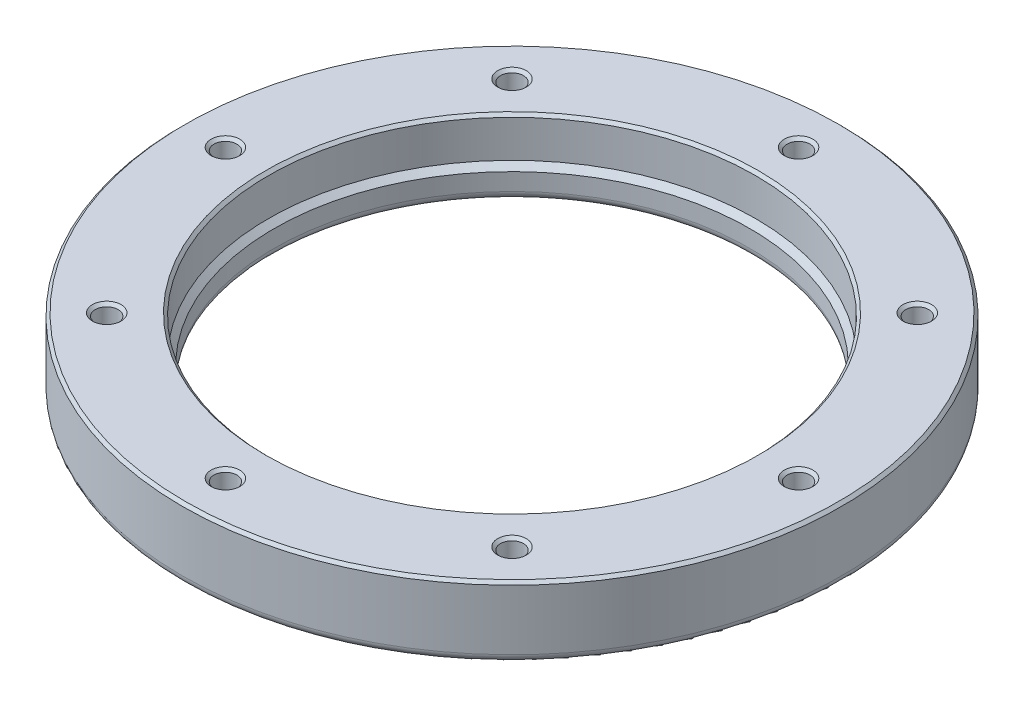
SolidWorks part; units mm, degrees
ref_plane "Front Plane" through (0, 0, 0) normal (0, 0, 1) x (1, 0, 0)
ref_plane "Top Plane" through (0, 0, 0) normal (0, 1, 0) x (1, 0, 0)
ref_plane "Right Plane" through (0, 0, 0) normal (1, 0, 0) x (0, 0, -1)
sketch "Sketch2" plane through (0, 0, 0) normal (0, 1, 0) x (1, 0, 0)
  circle A0 centre (0, 0) radius 115
  dimension "D1" = 230
extrude "Boss-Extrude1" add sketch "Sketch2" along normal blind 25
sketch "Sketch3" plane through (0, 25, 0) normal (0, 1, 0) x (1, 0, 0)
  circle A0 centre (0, 0) radius 85
  dimension "D1" = 170
extrude "Cut-Extrude1" cut sketch "Sketch3" against normal blind 16
sketch "Sketch4" plane through (0, 9, 0) normal (0, 1, 0) x (1, 0, 0)
  circle A0 centre (0, 0) radius 83
  dimension "D1" = 166
extrude "Cut-Extrude2" cut sketch "Sketch4" against normal through all
chamfer "Chamfer3" distance 2 angle 45 1 edges at (0, 9, 85)
chamfer "Chamfer5" distance 1 angle 45 2 edges at (0, 25, 85) (0, 25, 115)
fillet "Fillet1" radius 3 2 edges at (0, 0, 83) (0, 0, 115)
sketch "Sketch5" plane through (0, 25, 0) normal (0, 1, 0) x (1, 0, 0)
  line L0 (0, 0) -> (-169.6567, 0) construction
  circle A0 centre (-100, 0) radius 4
  circle A1 centre (-70.7107, 70.7107) radius 4
  circle A2 centre (0, 100) radius 4
  circle A3 centre (70.7107, 70.7107) radius 4
  circle A4 centre (100, 0) radius 4
  circle A5 centre (70.7107, -70.7107) radius 4
  circle A6 centre (0, -100) radius 4
  circle A7 centre (-70.7107, -70.7107) radius 4
  point P6 (-87.7602, 77.9295)
  point P21 (0, 0)
  dimension "D1" = 100
  dimension "D2" = 8
  dimension "D3" = 8
extrude "Cut-Extrude3" cut sketch "Sketch5" against normal blind 15
sketch "Sketch6" plane through (0, 0, 0) normal (0, -1, 0) x (1, 0, 0)
  line L0 (0, 0) -> (-154.1822, 0) construction
  circle A0 centre (-100, 0) radius 6
  circle A1 centre (-70.7107, 70.7107) radius 6
  circle A2 centre (0, 100) radius 6
  circle A3 centre (70.7107, 70.7107) radius 6
  circle A4 centre (100, 0) radius 6
  circle A5 centre (70.7107, -70.7107) radius 6
  circle A6 centre (0, -100) radius 6
  circle A7 centre (-70.7107, -70.7107) radius 6
  point P5 (-96.7859, 74.1369)
  point P6 (0, 0)
  point P22 (0, 0)
  dimension "D1" = 100
  dimension "D2" = 12
  dimension "D3" = 8
extrude "Cut-Extrude4" cut sketch "Sketch6" against normal blind 10
chamfer "Chamfer6" distance 1 angle 45 8 edges at (70.7107, 25, -66.7107) (100, 25, 4) (70.7107, 25, 74.7107) (0, 25, 104) (-70.7107, 25, 74.7107) (-100, 25, 4) (0, 25, -96) (-70.7107, 25, -66.7107)
